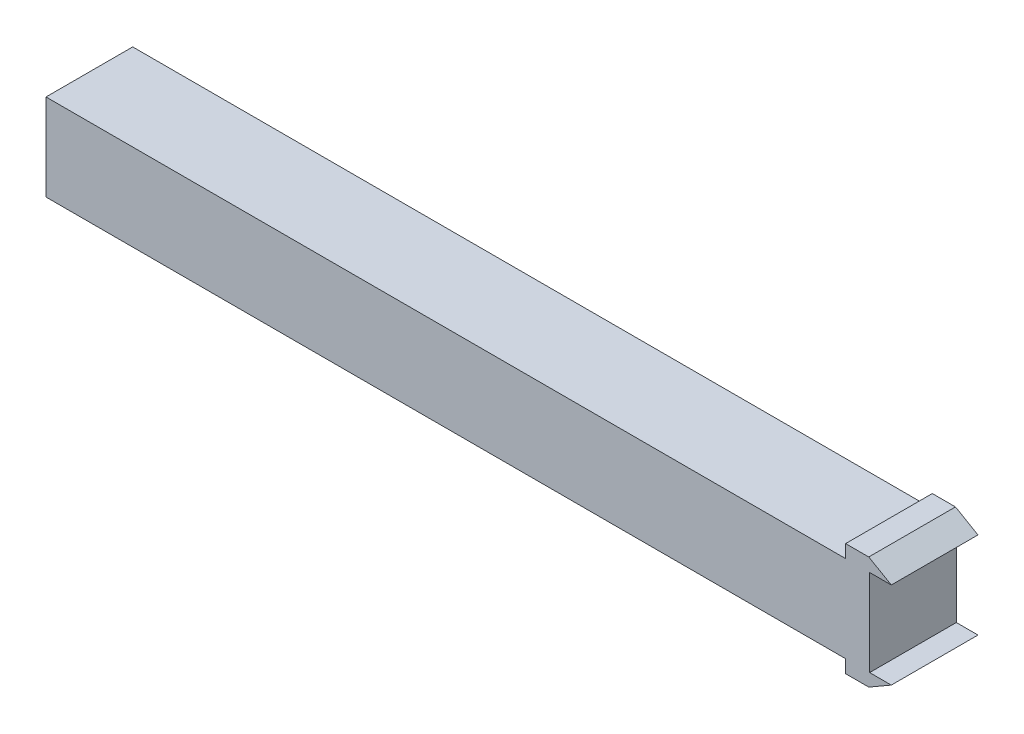
SolidWorks part; units mm, degrees
ref_plane "Front Plane" through (0, 0, 0) normal (0, 0, 1) x (1, 0, 0)
ref_plane "Top Plane" through (0, 0, 0) normal (0, 1, 0) x (1, 0, 0)
ref_plane "Right Plane" through (0, 0, 0) normal (1, 0, 0) x (0, 0, -1)
sketch "Sketch1" plane through (0, 0, 0) normal (0, 0, 1) x (1, 0, 0)
  line L1 (-95, -10) -> (95, -10)
  line L2 (-95, -10) -> (-95, 10)
  line L3 (-95, 10) -> (95, 10)
  line L4 (95, -10) -> (95, 10)
  line L5 (-95, -10) -> (95, 10) construction
  line L6 (-95, 10) -> (95, -10) construction
  point P0 (0, 0)
  dimension "D1" = 190
  dimension "D2" = 20
extrude "Boss-Extrude1" add sketch "Sketch1" along normal blind 20
sketch "Sketch2" plane through (0, 0, 20) normal (0, 0, 1) x (1, 0, 0)
  line L0 (95, 10) -> (-95, 10) construction
  line L1 (89.4573, 10) -> (89.4573, 13)
  line L2 (89.4573, 13) -> (94.8038, 13)
  line L3 (94.8038, 13) -> (100, 10)
  line L4 (100, 10) -> (95, 10)
  line L5 (95, 10) -> (89.4573, 10)
  dimension "D1" = 3
  dimension "D2" = 30
  dimension "D3" = 5.3466
  dimension "D4" = 5
extrude "Boss-Extrude2" add sketch "Sketch2" against normal blind 10
mirror "Mirror1" about plane through (0, 0, 0) normal (0, 1, 0) of "Boss-Extrude2"
mirror "Mirror2" about plane through (0, 0, 10) normal (0, 0, -1) of "Mirror1"
